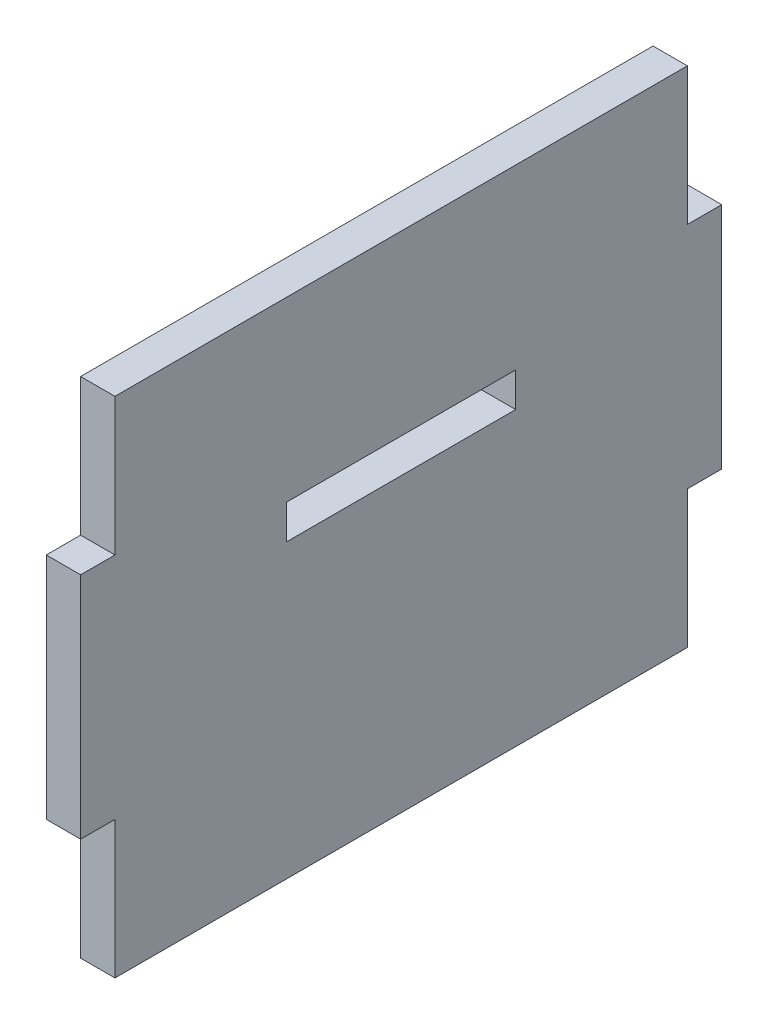
SolidWorks part; units mm, degrees
ref_plane "Front Plane" through (0, 0, 0) normal (0, 0, 1) x (1, 0, 0)
ref_plane "Top Plane" through (0, 0, 0) normal (0, 1, 0) x (1, 0, 0)
ref_plane "Right Plane" through (0, 0, 0) normal (1, 0, 0) x (0, 0, -1)
sketch "Sketch1" plane through (0, 0, 0) normal (1, 0, 0) x (0, 0, -1)
  line L0 (0, 44) -> (0, 32) construction
  line L1 (0, 0) -> (50, 0)
  line L2 (0, 0) -> (0, 12)
  line L3 (0, 44) -> (50, 44)
  line L4 (50, 0) -> (50, 12)
  line L5 (25, 44) -> (25, 0) construction
  line L6 (0, 12) -> (0, 0) construction
  line L7 (-3, 12) -> (0, 12)
  line L8 (-3, 12) -> (-3, 32)
  line L9 (-3, 32) -> (0, 32)
  line L11 (-3, 22) -> (25, 22) construction
  line L12 (53, 12) -> (50, 12)
  line L13 (0, 32) -> (0, 44)
  line L14 (53, 12) -> (53, 32)
  line L15 (53, 32) -> (50, 32)
  line L16 (50, 32) -> (50, 44)
  line L17 (25, 44) -> (25, 27) construction
  line L18 (0, 27) -> (50, 27) construction
  line L20 (15, 25.5) -> (35, 25.5)
  line L21 (15, 25.5) -> (15, 28.5)
  line L22 (15, 28.5) -> (35, 28.5)
  line L23 (35, 25.5) -> (35, 28.5)
  line L24 (15, 25.5) -> (35, 28.5) construction
  line L25 (15, 28.5) -> (35, 25.5) construction
  dimension "D1" = 50
  dimension "D2" = 44
  dimension "D3" = 20
  dimension "D4" = 3
  dimension "D5" = 17
  dimension "D6" = 20
  dimension "D7" = 3
extrude "Boss-Extrude1" add sketch "Sketch1" along normal blind 3
